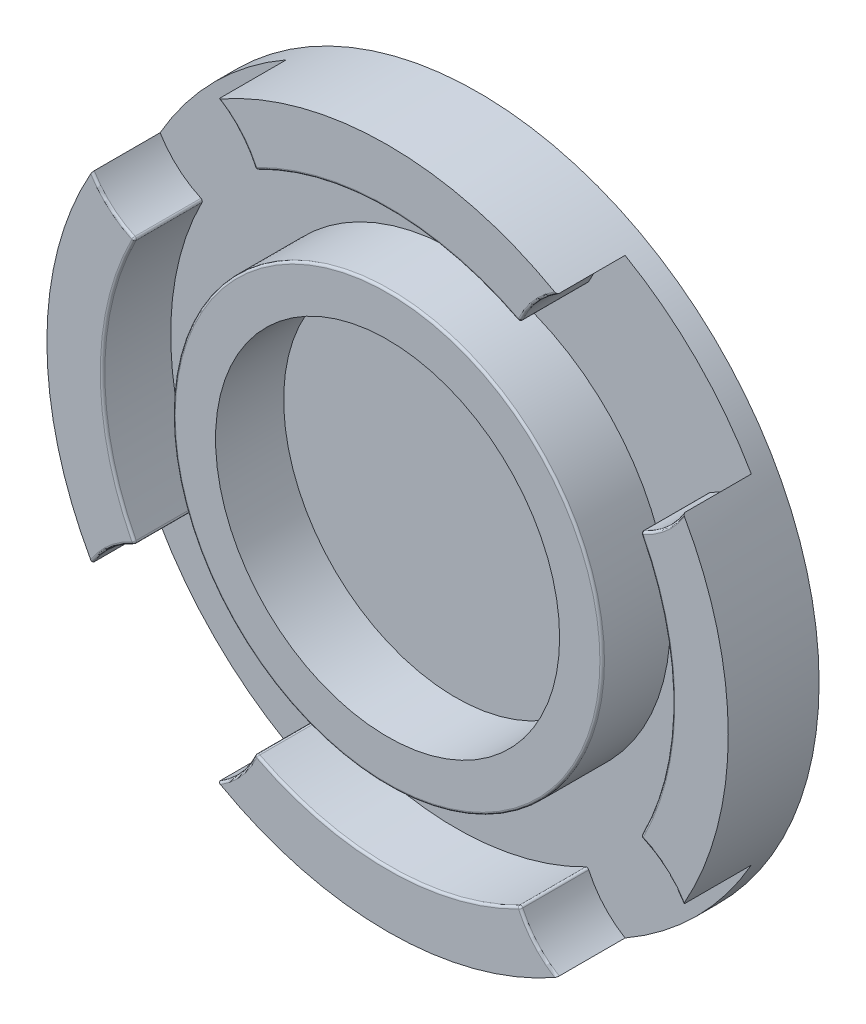
SolidWorks part; units mm, degrees
ref_plane "Front Plane" through (0, 0, 0) normal (0, 0, 1) x (1, 0, 0)
ref_plane "Top Plane" through (0, 0, 0) normal (0, 1, 0) x (1, 0, 0)
ref_plane "Right Plane" through (0, 0, 0) normal (1, 0, 0) x (0, 0, -1)
sketch "Sketch1" plane through (0, 0, 0) normal (0, 0, 1) x (1, 0, 0)
  line L0 (0, 0) -> (13.5, 0) construction
  line L1 (0, 0) -> (9.5459, 9.5459) construction
  circle A0 centre (0, 0) radius 9.45
  circle A1 centre (0, 0) radius 15
  arc A2 (-6.285, 11.9478) -> (-11.9478, 6.285) centre (0, 0) ccw construction
  arc A3 (7.4565, 13.0154) -> (5.815, 11.1215) centre (9.5459, 9.5459) ccw
  arc A4 (13.0154, -7.4565) -> (11.1215, -5.815) centre (9.5459, -9.5459) ccw
  arc A5 (-7.4565, -13.0154) -> (-5.815, -11.1215) centre (-9.5459, -9.5459) ccw
  arc A6 (-13.0154, 7.4565) -> (-11.1215, 5.815) centre (-9.5459, 9.5459) ccw
  arc A7 (-11.1215, 5.815) -> (-11.1215, -5.815) centre (0, 0) ccw
  arc A8 (11.9478, 6.285) -> (6.285, 11.9478) centre (0, 0) ccw construction
  arc A9 (6.285, -11.9478) -> (11.9478, -6.285) centre (0, 0) ccw construction
  arc A10 (-11.9478, -6.285) -> (-6.285, -11.9478) centre (0, 0) ccw construction
  arc A11 (5.815, 11.1215) -> (-5.815, 11.1215) centre (0, 0) ccw
  arc A12 (-5.815, -11.1215) -> (5.815, -11.1215) centre (0, 0) ccw
  arc A13 (11.1215, -5.815) -> (11.1215, 5.815) centre (0, 0) ccw
  arc A14 (-5.815, 11.1215) -> (-7.4565, 13.0154) centre (-9.5459, 9.5459) ccw
  arc A15 (11.1215, 5.815) -> (13.0154, 7.4565) centre (9.5459, 9.5459) ccw
  arc A16 (5.815, -11.1215) -> (7.4565, -13.0154) centre (9.5459, -9.5459) ccw
  arc A17 (-11.1215, -5.815) -> (-13.0154, -7.4565) centre (-9.5459, -9.5459) ccw
  circle A18 centre (0, 0) radius 7.575
  point P17 (0, 0)
  dimension "D1" = 18.9
  dimension "D2" = 30
  dimension "D3" = 27
  dimension "D4" = 45
  dimension "D5" = 8.1
  dimension "D6" = 4
  dimension "D7" = 25.1
  dimension "D8" = 15.15
extrude "Boss-Extrude1" add sketch "Sketch1" along normal blind 3 contours A14 A11 A3 A1 | A15 A13 A4 A1 | A16 A12 A5 A1 | A17 A7 A6 A1 | A0 A18 region at (-9.1827, 0, 0) region at (13.2722, 0, 0) region at (0, 13.2722, 0) region at (0, -13.2722, 0) region at (-13.2722, 0, 0)
sketch "Sketch2" plane through (0, 0, 0) normal (0, 0, 1) x (1, 0, 0)
  circle A0 centre (0, 0) radius 15
extrude "Boss-Extrude2" add sketch "Sketch2" against normal blind 1
fillet "Fillet1" radius 0.1 8 edges at (-5.815, -11.1215, 1.5) (5.815, -11.1215, 1.5) (11.1215, -5.815, 1.5) (11.1215, 5.815, 1.5) (5.815, 11.1215, 1.5) (-5.815, 11.1215, 1.5) (-11.1215, 5.815, 1.5) (-11.1215, -5.815, 1.5)
fillet "Fillet2" radius 0.1 21 edges at (6.5204, 12.2382, 3) (5.7991, 11.165, 3) (-6.5204, 12.2382, 3) (-5.7991, 11.165, 3) (12.2382, -6.5204, 3) (11.165, -5.7991, 3) (12.2382, 6.5204, 3) (11.165, 5.7991, 3) (-6.5204, -12.2382, 3) (-5.7991, -11.165, 3) (6.5204, -12.2382, 3) (5.7991, -11.165, 3) (-12.2382, 6.5204, 3) (-11.165, 5.7991, 3) (-12.2382, -6.5204, 3) (-11.165, -5.7991, 3) (0, 12.55, 3) (12.55, 0, 3) (0, -12.55, 3) (9.45, 0, 3) (-12.55, 0, 3)
